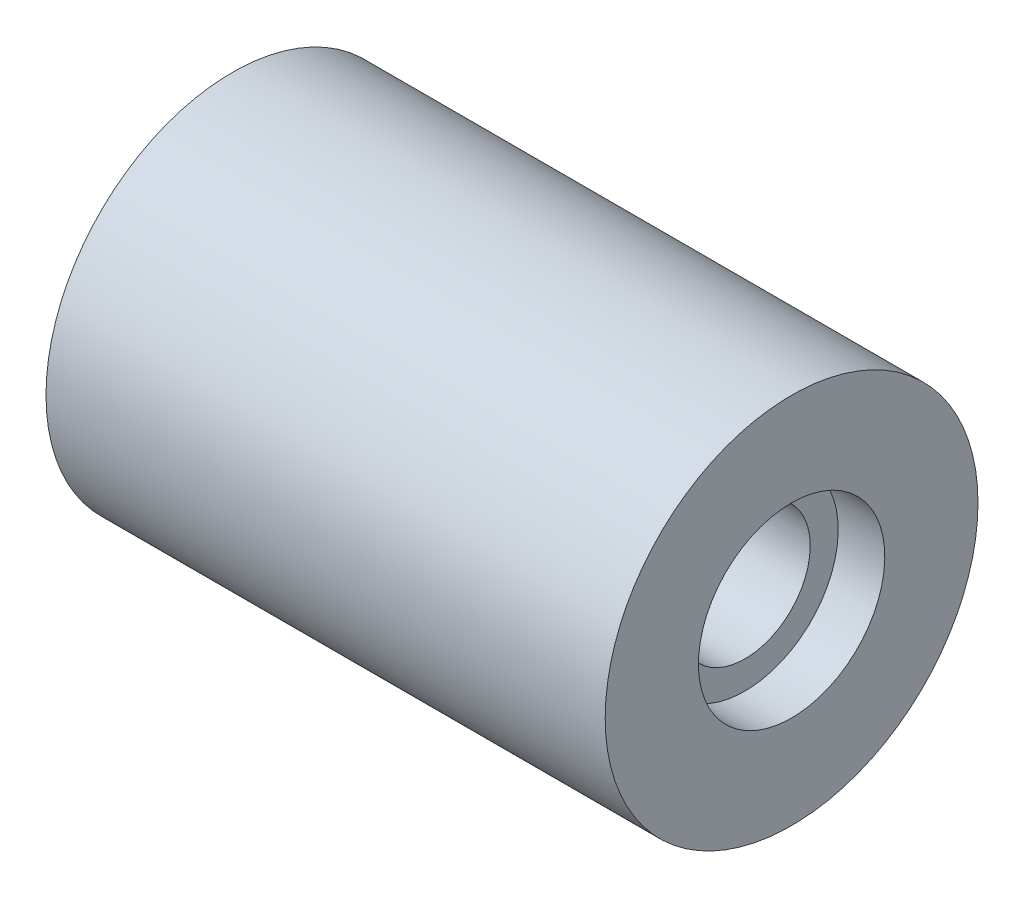
SolidWorks part; units mm, degrees
ref_plane "Front Plane" through (0, 0, 0) normal (0, 0, 1) x (1, 0, 0)
ref_plane "Top Plane" through (0, 0, 0) normal (0, 1, 0) x (1, 0, 0)
ref_plane "Right Plane" through (0, 0, 0) normal (1, 0, 0) x (0, 0, -1)
sketch "Sketch1" plane through (0, 0, 0) normal (0, 0, 1) x (1, 0, 0)
  line L0 (-30.6578, 10.6299) -> (-30.6578, 11.9507)
  line L1 (-49.53, 0) -> (-49.53, 12.7)
  line L2 (-49.53, 12.7) -> (-34.29, 12.7)
  line L3 (-34.29, 12.7) -> (-34.29, 10.6299)
  line L4 (-34.29, 10.6299) -> (-33.02, 10.6299)
  line L5 (-28.8798, 10.6299) -> (-28.8798, 11.9507)
  line L6 (-28.8798, 11.9507) -> (-26.5176, 11.9507)
  line L7 (-26.5176, 11.9507) -> (-26.5176, 10.6299)
  line L8 (-26.5176, 10.6299) -> (-21.59, 10.6299)
  line L9 (-21.59, 10.6299) -> (-21.59, 8.89)
  line L10 (-21.59, 8.89) -> (-6.35, 8.89)
  line L11 (-6.35, 8.89) -> (-6.35, 12.7)
  line L12 (-6.35, 12.7) -> (0, 12.7)
  line L16 (0, 0) -> (-49.53, 0)
  line L17 (-30.6578, 11.9507) -> (-33.02, 11.9507)
  line L18 (-33.02, 11.9507) -> (-33.02, 10.6299)
  line L19 (-30.6578, 10.6299) -> (-28.8798, 10.6299)
  line L20 (0, 0) -> (0, 12.7)
  dimension "D1" = 6.35
  dimension "D2" = 2.3622
  dimension "D3" = 1.3208
  dimension "D5" = 8.89
  dimension "D6" = 15.24
  dimension "D9" = 1.27
  dimension "D10" = 12.7
  dimension "D11" = 15.24
  dimension "D7" = 12.7
  dimension "D4" = 11.9507
  dimension "D8" = 12.7
  dimension "D12" = 1.778
sketch "Sketch2" plane through (0, 0, 0) normal (1, 0, 0) x (0, 0, -1)
  circle A0 centre (0, 0) radius 25.4
  dimension "D1" = 50.8
extrude "Boss-Extrude1" add sketch "Sketch2" against normal blind 76.2
revolve "Cut-Revolve1" cut sketch "Sketch1" angle 360 about L16
equation "\"lip_seal_width\"= 0.25in"
equation "\"D1@Sketch1\"=\"lip_seal_width\""
equation "\"Cavity_Depth\" = 0.031in"
equation "\"Cavity_Width\" = 0.031in"
equation "\"Tooth_Width\" = .01in"
equation "\"Shaft_Seal_OD\"= 17mm'diameter at seal area"
equation "\"Shaft_clearance\"= .002in"
equation "\"O-Ring_ID\"= .801in"
equation "\"O-Ring_CS\"= .070in"
equation "\"Shaft_OD\"= .5in"
equation "\"D5@Sketch1\"=\"Shaft_OD\"/2 + .1in"
equation "\"post_laby_len\"= 1.25in"
equation "\"D6@Sketch1\"=\"post_laby_len\" - \"lip_seal_width\"-.4in"
equation "\"lip_seal_OD\"= 1in"
equation "\"D7@Sketch1\"=\"lip_seal_OD\"/2"
equation "\"Casing_OD\" = 2in"
equation "\"D1@Sketch2\"=\"Casing_OD\""
equation "\"D4@Sketch1\"=\"O-Ring_ID\"/2 + \"O-Ring_CS\""
